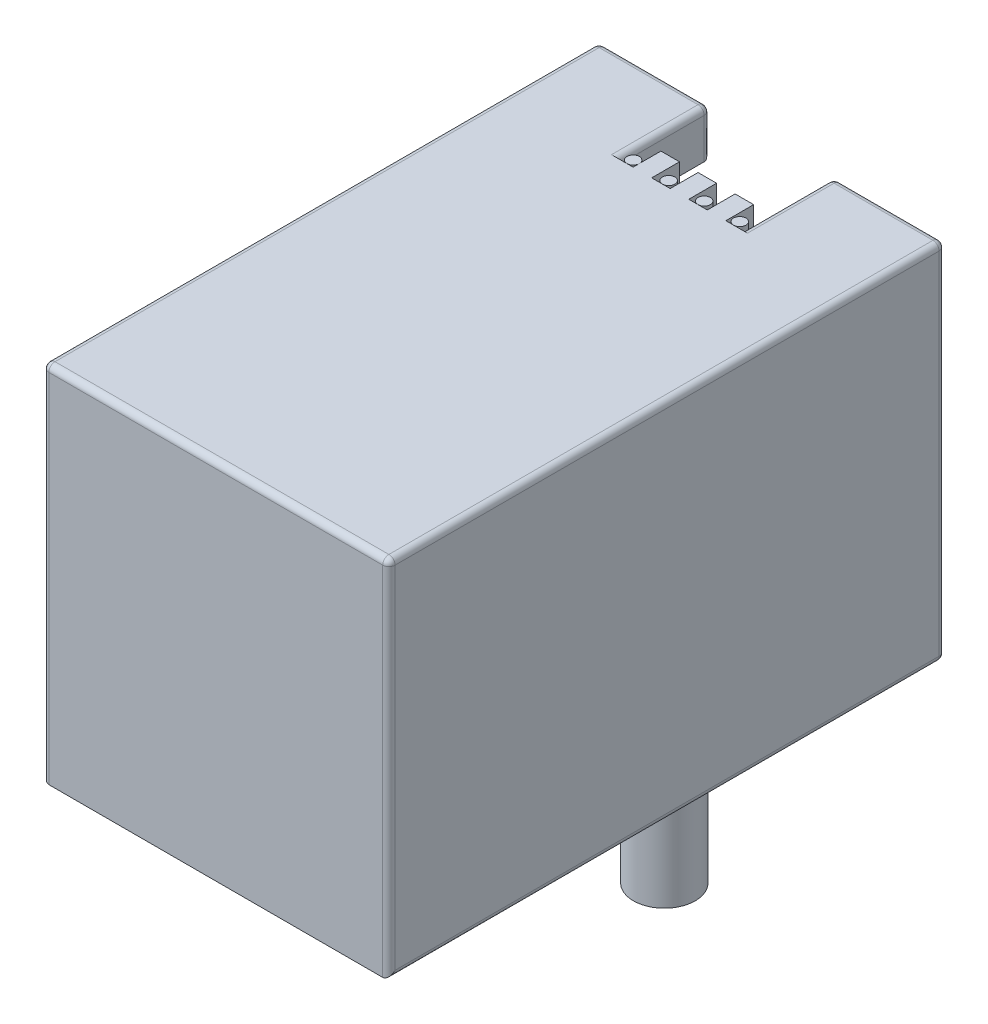
SolidWorks part; units mm, degrees
material "ABS PC"
ref_plane "Front Plane" through (0, 0, 0) normal (0, 0, 1) x (1, 0, 0)
ref_plane "Top Plane" through (0, 0, 0) normal (0, 1, 0) x (1, 0, 0)
ref_plane "Right Plane" through (0, 0, 0) normal (1, 0, 0) x (0, 0, -1)
sketch "Sketch1" plane through (0, 0, 0) normal (0, 0, 1) x (1, 0, 0)
  line L0 (-5.6, 0) -> (5.6, 0) construction
  line L1 (-5.6, 5.875) -> (5.6, 5.875)
  line L2 (-5.6, 5.875) -> (-5.6, -5.875)
  line L3 (-5.6, -5.875) -> (5.6, -5.875)
  line L4 (5.6, 5.875) -> (5.6, -5.875)
  dimension "D1" = 11.2
  dimension "D2" = 11.75
extrude "Extrude1" add sketch "Sketch1" along normal mid plane 18
sketch "Sketch2" plane through (0, 0, -9) normal (0, 0, -1) x (-1, 0, 0)
  line L0 (0, 4.375) -> (0, -5.875) construction
  line L1 (-4.1, 4.375) -> (-4.1, -3.625)
  line L2 (-5.6, 5.875) -> (5.6, 5.875) construction
  line L3 (4.1, 4.375) -> (-4.1, 4.375)
  line L4 (-5.6, -5.875) -> (-5.6, 5.875) construction
  line L5 (-2.85, -4.875) -> (-1.5, -4.875)
  line L6 (-4.1, -3.625) -> (-2.85, -3.625)
  line L7 (1.5, -4.875) -> (1.5, -5.875)
  line L8 (2.85, -4.875) -> (1.5, -4.875)
  line L9 (-2.85, -3.625) -> (-2.85, -4.875)
  line L10 (-1.5, -4.875) -> (-1.5, -5.875)
  line L11 (2.85, -3.625) -> (2.85, -4.875)
  line L12 (4.1, -3.625) -> (2.85, -3.625)
  line L13 (-1.5, -5.875) -> (1.5, -5.875)
  line L14 (0, 5.875) -> (0, -5.875) construction
  line L15 (5.6, -5.875) -> (-5.6, -5.875) construction
  line L16 (4.1, 4.375) -> (4.1, -3.625)
  point P19 (0, -5.555)
  point P28 (0, 4.375)
  dimension "D2" = 1.25
  dimension "D3" = 1.5
  dimension "D4" = 1.5
  dimension "D5" = 1.5
  dimension "D6" = 1
extrude "Cut-Extrude1" cut sketch "Sketch2" against normal blind 8
sketch "Sketch3" plane through (0, -5.875, 0) normal (0, -1, 0) x (1, 0, 0)
  line L0 (-3.81, -1.7) -> (-3.81, 9) construction
  line L1 (0, -1.7) -> (0, 9) construction
  line L2 (-3.81, -1.7) -> (-5.6, -1.7) construction
  line L3 (0, -1.7) -> (-3.81, -1.7) construction
  line L5 (-5.6, 9) -> (-5.6, -9) construction
  line L6 (-5.6, 9) -> (5.6, 9) construction
  circle A0 centre (-3.81, -1.7) radius 1
  circle A1 centre (3.81, -1.7) radius 1
  dimension "D1" = 2
  dimension "D2" = 10.7
  dimension "D3" = 1.79
extrude "Extrude2" add sketch "Sketch3" along normal blind 3.5
sketch "Sketch4" plane through (0, 4.375, 0) normal (0, -1, 0) x (1, 0, 0)
  line L0 (0, -6) -> (0, -9) construction
  line L2 (-4.1, -9) -> (4.1, -9) construction
  line L3 (-0.3, -6) -> (-0.9, -6)
  line L4 (2, -9) -> (-2, -9)
  line L5 (2, -9) -> (2, -6)
  line L6 (0.3, -6) -> (0.9, -6)
  line L7 (-2, -9) -> (-2, -6)
  line L8 (0.3, -6) -> (-0.3, -6) construction
  line L9 (0.3, -6) -> (0.3, -6.9)
  line L10 (0.3, -6.9) -> (-0.3, -6.9)
  line L12 (1.5, -6) -> (1.5, -6.9)
  line L13 (1.5, -6.9) -> (0.9, -6.9)
  line L14 (0.9, -6) -> (0.9, -6.9)
  line L15 (-0.9, -6) -> (-0.9, -6.9)
  line L16 (-0.9, -6.9) -> (-1.5, -6.9)
  line L17 (-1.5, -6) -> (-1.5, -6.9)
  line L18 (0.3, -6) -> (0.3, -6.9)
  line L19 (0.3, -6.9) -> (-0.3, -6.9)
  line L20 (-0.3, -6) -> (-0.3, -6.9)
  line L21 (-1.5, -6) -> (-2, -6)
  line L22 (1.5, -6) -> (2, -6)
  line L23 (-0.3, -6) -> (-0.3, -6.9) [skipped]
  point P2 (1.75, -6)
  line M1 (-4.1, -9) -> (4.1, -9)
  dimension "D1" = 4
  dimension "D2" = 3
  dimension "D3" = 0.9
  dimension "D4" = 0.6
extrude "Cut-Extrude2" cut sketch "Sketch4" against normal up to surface (1.5 mm away) contours L22 L12 L13 L14 L6 L9 L10 L20 L3 L15 L16 L17 L21 L7 L5 M1 region at (0, 4.375, -7.6639) up to face at (0, 5.875, 0)
sketch "Sketch6" plane through (0, 0, -1) normal (0, 0, -1) x (-1, 0, 0)
  line L14 (-2.35, -4.375) -> (-1.5, -4.375)
  line L15 (-2.35, -3.625) -> (-2.35, -4.375)
  line L16 (-2.35, -4.375) -> (-1.5, -4.375) construction
  line L17 (-2.35, -3.625) -> (-2.35, -4.375) construction
  line L18 (-2.35, -4.375) -> (2.35, -4.375)
  line L19 (2.35, -4.375) -> (2.35, 0)
  line L20 (1.5, -4.375) -> (2.35, -4.375)
  line L21 (2.35, -4.375) -> (2.35, -3.625)
  line L22 (1.5, -4.375) -> (2.35, -4.375) construction
  line L23 (2.35, -4.375) -> (2.35, -3.625) construction
  line L24 (2.35, 0) -> (-2.35, 0)
  line L25 (-2.35, 0) -> (-2.35, -4.375)
  dimension "D1" = 0.5
  dimension "D2" = 0.5
extrude "Cut-Extrude3" cut sketch "Sketch6" against normal blind 0.5
sketch "Sketch7" plane through (0, 0, -1) normal (0, 0, -1) x (-1, 0, 0)
  line L0 (1.5, 4.375) -> (2, 4.375) construction
  line L1 (0.3, 4.375) -> (0.9, 4.375) construction
  line L2 (-0.3, 4.375) -> (-0.9, 4.375) construction
  line L3 (-1.5, 4.375) -> (-2, 4.375) construction
  line L4 (1.5, 4.375) -> (2, 4.375)
  line L5 (0.3, 4.375) -> (0.9, 4.375)
  line L6 (-0.3, 4.375) -> (-0.9, 4.375)
  line L7 (-1.5, 4.375) -> (-2, 4.375)
  line L8 (-2, 4.375) -> (-2, -2.1875)
  line L9 (-2.35, -2.1875) -> (2.35, -2.1875) construction
  line L10 (-2.35, 0) -> (-2.35, -4.375) construction
  line L11 (2.35, -4.375) -> (2.35, 0) construction
  line L12 (-1.5, 4.375) -> (-1.5, -2.1875)
  line L13 (-1.5, -2.1875) -> (-2, -2.1875)
  line L14 (-0.9, 4.375) -> (-0.9, -2.1875)
  line L15 (-0.9, -2.1875) -> (-0.3, -2.1875)
  line L16 (-0.3, -2.1875) -> (-0.3, 4.375)
  line L17 (0.3, 4.375) -> (0.3, -2.1875)
  line L18 (0.3, -2.1875) -> (0.9, -2.1875)
  line L19 (0.9, -2.1875) -> (0.9, 4.375)
  line L20 (1.5, 4.375) -> (1.5, -2.1875)
  line L21 (1.5, -2.1875) -> (2, -2.1875)
  line L22 (2, -2.1875) -> (2, 4.375)
extrude "Cut-Extrude4" cut sketch "Sketch7" against normal blind 1
ref_plane "Plane1" through (1.75, 0, 0) normal (1, 0, 0) x (0, 0, -1)
sketch "Sketch9" plane through (1.75, 0, 0) normal (1, 0, 0) x (0, 0, -1)
  line L0 (6, 4.375) -> (6, 5.875)
  line L1 (5.8347, 4.178) -> (0, 3.1492)
  line L2 (0, 4.375) -> (0, -2.1875) construction
  arc A0 (6, 4.375) -> (5.8347, 4.178) centre (5.8, 4.375) cw
  dimension "D2" = 0.2
  dimension "D1" = 100
sketch "Sketch10" plane through (0, 5.875, 0) normal (0, 1, 0) x (1, 0, 0)
  line L0 (2, 6) -> (1.5, 6) construction
  line L1 (1.75, 6) -> (1.75, 6.2) construction
  circle A0 centre (1.75, 6.2) radius 0.2
  dimension "D1" = 0.4
sweep "Sweep1" add profiles "Sketch10" path "Sketch9"
pattern_linear "LPattern2" count 4 spacing 1.15 along (-1, 0, 0) of bodies 107
fillet "Fillet1" radius 0.2 40 edges at (2, 5.125, -9) (-2, 5.875, -7.5) (-2, 5.125, -9) (-3.05, 4.375, -9) (-4.1, 0.375, -9) (-3.475, -3.625, -9) (-2.85, -4.25, -9) (-2.175, -4.875, -9) (1.5, -5.375, -9) (2.175, -4.875, -9) (2.85, -4.25, -9) (3.475, -3.625, -9) (4.1, 0.375, -9) (3.05, 4.375, -9) (-2.85, -3.625, -5) (-2.85, -4.875, -5) (2.85, -3.625, -5) (2.85, -4.875, -5) (0, -5.875, -1) (1.5, -5.875, -5) (-1.5, -4.875, -5) (-1.5, -5.875, -5) (-5.6, -5.875, 0) (5.6, -5.875, 0) (0, 5.875, 9) (-5.6, 5.875, 0) (5.6, 5.875, 0) (2, 5.875, -7.5) (-3.8, 5.875, -9) (-5.6, 0, -9) (-1.5, -5.375, -9) (-3.55, -5.875, -9) (3.55, -5.875, -9) (5.6, 0, -9) (3.8, 5.875, -9) (1.5, -4.875, -5) (4.1, -3.625, -5) (-4.1, -3.625, -5) (-5.6, 0, 9) (5.6, 0, 9)
ref_plane "Plane2" through (0, 0.375, 0) normal (0, -1, 0) x (1, 0, 0)
sketch "Sketch11" plane through (0, 0.375, 0) normal (0, -1, 0) x (1, 0, 0)
  line L0 (0, -13) -> (0, 0) construction
  dimension "D1" = 13
ref_point "Point1"
ref_axis "Axis1" through (0, 0.375, -4.5147) along (0, 0, -1)
